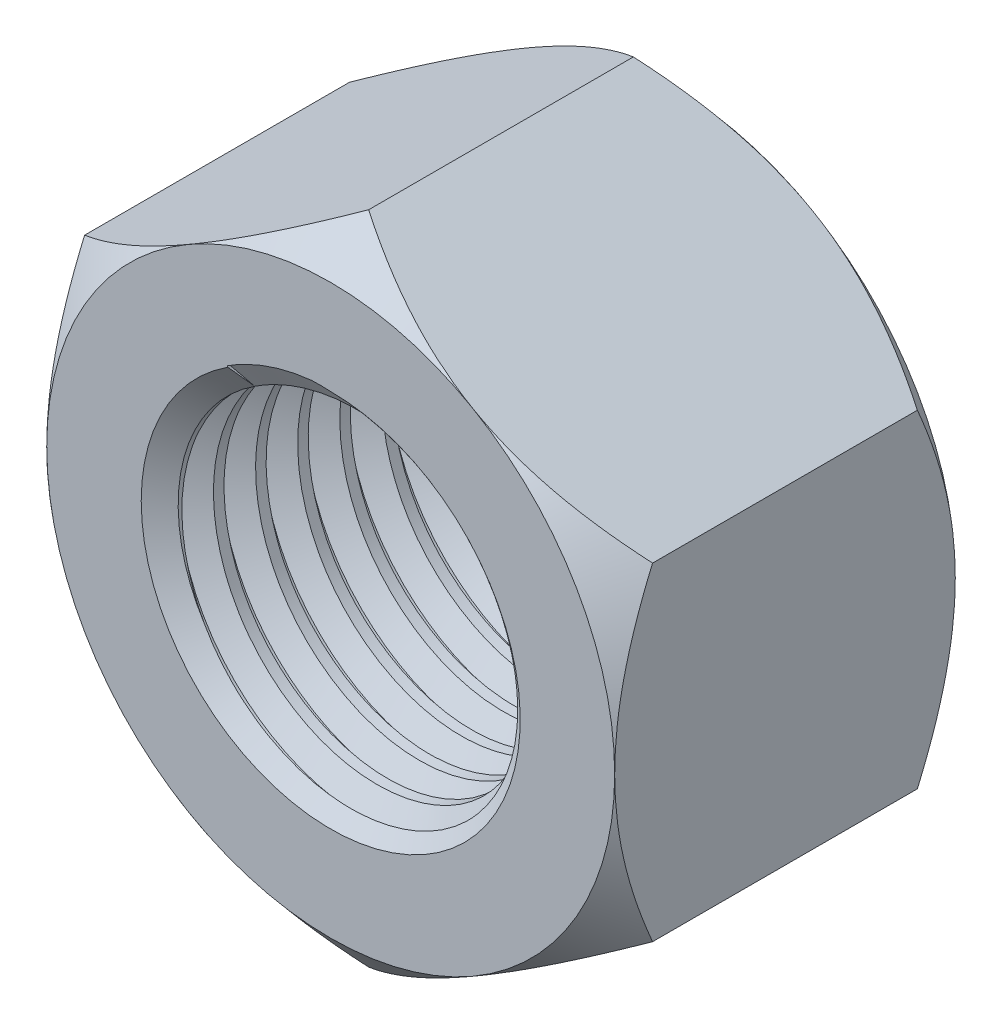
SolidWorks part; units mm, degrees
extrude "BaseNut" add sketch "BaseNutSke" against normal blind 8.5598
sketch "BaseNutSke" plane through (0, 0, 0) normal (0, 0, 1) x (1, 0, 0)
  line L6 (7.1374, 4.1208) -> (7.1374, -4.1208)
  line L7 (-7.1374, 4.1208) -> (-7.1374, -4.1208)
  line L8 (7.1374, 4.1208) -> (0, 8.2416)
  line L9 (0, 8.2416) -> (-7.1374, 4.1208)
  line L10 (-7.1374, -4.1208) -> (0, -8.2416)
  line L11 (0, -8.2416) -> (7.1374, -4.1208)
  circle A0 centre (0, 0) radius 4.2164
  dimension "D2" = 7.1374
  dimension "D3" = 7.1374
  dimension "D1" = 120
  dimension "D4" = 7.1374
cosmetic thread "ThreadCosmetic" [suppressed] parameters "Thread_major"=9.525
pattern_linear "ThdSchPat" [suppressed]
revolve "ThreadSchematic" [suppressed] cut sketch "ThdSchSke" angle 360 about L6
sketch "ThdSchSke" plane through (0, 0, 0) normal (0, 1, 0) x (1, 0, 0)
  line L0 (-4.7625, 0.0254) -> (-4.2164, 0.4078)
  line L1 (-4.2164, 0.4078) -> (-2.1082, 0.4078)
  line L2 (-2.1082, 0.4078) -> (-2.1082, -0.357)
  line L3 (-2.1082, -0.357) -> (-4.2164, -0.357)
  line L4 (-4.2164, -0.357) -> (-4.7625, 0.0254)
  line L5 (-3.175, 1.0592) -> (3.175, 1.0592) construction
  line L6 (0, 1.0592) -> (0, -2.9874) construction
  line L7 (0, 8.152) -> (0, 0.3824) construction
  dimension "SideAngle" = 55
  dimension "Advance" = 1.0592
  dimension "D1" = 0.0254
ref_plane "Plane1" through (0, 0, 0) normal (0, 0, 1) x (1, 0, 0)
ref_plane "Plane2" through (0, 0, 0) normal (0, 1, 0) x (1, 0, 0)
ref_plane "Plane3" through (0, 0, 0) normal (1, 0, 0) x (0, 0, -1)
sketch "Sketch4" plane through (0, 0, 0) normal (1, 0, 0) x (0, 0, -1)
  line L0 (8.5598, 7.1374) -> (8.1534, 7.1374)
  line L1 (8.5598, 7.1374) -> (8.5598, 20.9416)
  line L2 (8.1534, 20.9416) -> (8.5598, 20.9416)
  line L3 (8.1534, 20.9416) -> (8.1534, 7.1374)
  line L4 (0, 0) -> (34.925, 0) construction
  line L6 (8.5598, 4.1208) -> (8.5598, 8.2416) construction
  line L7 (0, 7.1374) -> (-12.7, 7.1374)
  line L8 (0, 4.1208) -> (0, 8.2416) construction
  line L9 (0.9525, 8.2416) -> (0.9525, 20.9416)
  line L10 (0.9525, 20.9416) -> (-12.7, 20.9416)
  line L11 (-12.7, 20.9416) -> (-12.7, 7.1374)
  line L12 (0, 7.1374) -> (0.9525, 8.2416)
  line L14 (0, 4.1208) -> (0, -4.1208) construction
  line L15 (8.5598, 8.2416) -> (0, 8.2416) construction
  dimension "D1" = 7.1374
  dimension "D2" = 0.9525
  dimension "D3" = 12.7
  dimension "D4" = 12.7
revolve "Bearing-Face" [suppressed] cut sketch "Sketch4" angle 360 about L4
sketch "Sketch3" plane through (0, 0, 0) normal (1, 0, 0) x (0, 0, -1)
  line L0 (8.5598, 7.1374) -> (7.6073, 8.2416)
  line L1 (7.6073, 8.2416) -> (7.6073, 20.9416)
  line L2 (7.6073, 20.9416) -> (21.2598, 20.9416)
  line L3 (21.2598, 20.9416) -> (21.2598, 7.1374)
  line L4 (21.2598, 7.1374) -> (8.5598, 7.1374)
  line L5 (8.5598, 4.1208) -> (8.5598, 8.2416) construction
  line L6 (8.5598, 8.2416) -> (0, 8.2416) construction
  line L7 (0, 0) -> (38.6776, 0) construction
  line L8 (8.5598, 0) -> (0, 0) construction
  line L9 (4.2799, 8.2416) -> (4.2799, 44.222) construction
  line L10 (0.9525, 20.9416) -> (-12.7, 20.9416)
  line L11 (-12.7, 20.9416) -> (-12.7, 7.1374)
  line L12 (-12.7, 7.1374) -> (0, 7.1374)
  line L13 (0, 7.1374) -> (0.9525, 8.2416)
  line L14 (0.9525, 8.2416) -> (0.9525, 20.9416)
  line L16 (8.5598, 8.2416) -> (0, 8.2416) construction
  dimension "D1" = 7.1374
  dimension "D2" = 0.9525
  dimension "D4" = 12.7
  dimension "D3" = 12.7
revolve "Double-Chamfer" cut sketch "Sketch3" angle 360 about L7
sketch "Sketch5" plane through (0, 0, 0) normal (1, 0, 0) x (0, 0, -1)
  line L0 (8.5344, 4.7625) -> (8.1138, 4.1618)
  line L1 (8.5852, 4.7625) -> (8.5344, 4.7625)
  line L2 (8.5852, 4.7625) -> (8.5852, 4.1618)
  line L3 (8.5852, 4.1618) -> (8.1138, 4.1618)
  line L6 (-0.0508, 4.7625) -> (0, 4.7625)
  line L7 (0, 4.7625) -> (0.4206, 4.1618)
  line L9 (0.4206, 4.1618) -> (-0.0508, 4.1618)
  line L10 (-0.0508, 4.1618) -> (-0.0508, 4.7625)
  line L11 (25.0375, 0) -> (38.388, 0) construction
  line L12 (8.5598, 0) -> (0, 0) construction
  dimension "D1" = 35
  dimension "D2" = 0.0508
  dimension "ThreadMajor" = 4.7625
  dimension "Offset1" = 8.5852
revolve "EndChamfer" cut sketch "Sketch5" angle 360 about L11
thread "Thread1" pitch 1.0583 method cut profile "Thread Profile1" start angle 0, offset 0, length 0, pitch 1.0583, diameter 8.4328
ref_plane "Plane4" through (4.2164, 0, -8.152) normal (0, -1, 0) x (1, 0, 0)
sketch "Thread Profile1" plane through (4.2164, 0, -8.152) normal (0, -1, 0) x (1, 0, 0)
  line L0 (0, 0) -> (0, 1.0583) construction
  line L1 (0, 0) -> (0.5728, 0.3307)
  line L2 (0.5728, 0.3307) -> (0.5728, 0.463)
  line L3 (0.5728, 0.463) -> (0, 0.7937)
  line L4 (0.5728, 0.3969) -> (0, 0.3969) construction
  line L11 (0, 0) -> (0, 0.7937)
  point P2 (0, 0)
  dimension "Pitch" = 1.0583
  dimension "Profile_Angle" = 60
  dimension "Profile_Land" = 0.1323
  dimension "Profile_Height" = 0.5728
equation "\"D2@BaseNutSke\" = \"Width_flats@BaseNutSke\" / 2"
equation "\"D3@BaseNutSke\" = \"Width_flats@BaseNutSke\" / 2"
equation "\"D1@Sketch3\" = \"Width_flats@BaseNutSke\" /2"
equation "\"D2@Sketch3\" = \"Thread_major@ThreadCosmetic\" *.1"
equation "\"D1@Sketch4\" = \"D2@BaseNutSke\""
equation "\"D2@Sketch4\" = \"Thread_major@ThreadCosmetic\" *.10"
equation "\"D4@BaseNutSke\" = \"D3@BaseNutSke\""
equation "\"Thread_major@ThdSchSke\" = \"Thread_major@ThreadCosmetic\""
equation "\"Tap_Drill@ThdSchSke\" = \"Tap_drill@BaseNutSke\""
equation "\"OverCut@ThdSchSke\" = \"Tap_Drill@ThdSchSke\" * 0.5"
equation "\"Num_threads@ThdSchPat\" = int(  ( \"Thickness@BaseNut\" - 0.002 ) / \"Advance@ThdSchSke\" + 0.999 )  + 1"
equation "\"Advance@ThdSchPat\" = ( \"Thickness@BaseNut\" - 0.002 ) /  (\"Num_threads@ThdSchPat\" - 1) 'relax it"
equation "' \"Num_threads@ThdSchPat\" = \"Num_threads@ThdSchPat\" - sgn( \"Num_threads@ThdSchPat\" - 1) '---chamfered tips only---"
equation "\"ThreadMajor@Sketch5\" = \"Thread_major@ThreadCosmetic\" * 0.5"
equation "\"ChamferDepth@Sketch5\" = (\"Thread_major@ThreadCosmetic\" - \"Tap_drill@BaseNutSke\") * 0.55"
equation "\"Offset1@Sketch5\" = \"Thickness@BaseNut\" + 0.001"
equation "\"Offset2@Sketch5\" = \"Offset1@Sketch5\" + 0.002"
